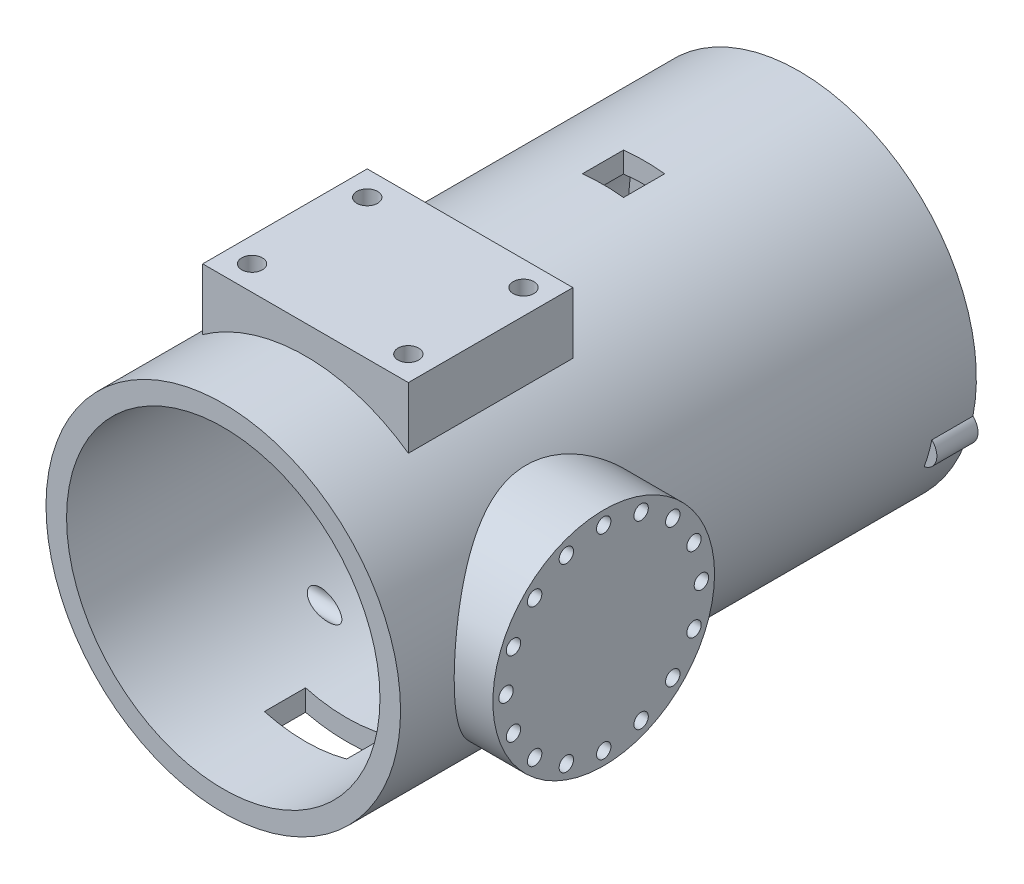
SolidWorks part; units mm, degrees
other "Markup1"
sketch "Sketch14" plane through (-43.1, 43.1, 140) normal (-0.1765, 0.0048, 0.9843) x (0.9842, -0.0149, 0.1765)
other "Markup2"
sketch "Sketch23" plane through (45.1, -43.1, 140) normal (0.9491, -0.0629, 0.3087) x (0.311, 0.031, -0.9499)
ref_plane "Front Plane" through (0, 0, 0) normal (0, 0, 1) x (1, 0, 0)
ref_plane "Top Plane" through (0, 0, 0) normal (0, 1, 0) x (1, 0, 0)
ref_plane "Right Plane" through (0, 0, 0) normal (1, 0, 0) x (0, 0, -1)
sketch "Sketch1" plane through (0, 0, 0) normal (0, 0, 1) x (1, 0, 0)
  circle A1 centre (0, 0) radius 43.1
  dimension "D1" = 86.2
extrude "Main Body" add sketch "Sketch1" along normal blind 140
ref_plane "Plane1" through (0, 43.1, 0) normal (0, 1, 0) x (1, 0, 0)
sketch "Sketch34" [suppressed] plane through (0, 43.1, 0) normal (0, 1, 0) x (1, 0, 0)
  line L6 (-5, -13) -> (5, -13)
  line L8 (-5, -13) -> (-5, -3)
  line L9 (-5, -3) -> (5, -3)
  line L10 (5, -13) -> (5, -3)
  line L11 (-5, -13) -> (5, -3) construction
  line L12 (-5, -3) -> (5, -13) construction
  point P0 (0, -8)
  dimension "D1" = 8
  dimension "D2" = 10
  dimension "D3" = 10
sketch "Sketch6" plane through (0, 43.1, 0) normal (0, 1, 0) x (1, 0, 0)
  line L2 (-5, -47.7) -> (5, -47.7)
  line L3 (-5, -47.7) -> (-5, -37.7)
  line L4 (-5, -37.7) -> (5, -37.7)
  line L5 (5, -47.7) -> (5, -37.7)
  line L6 (-5, -47.7) -> (5, -37.7) construction
  line L7 (-5, -37.7) -> (5, -47.7) construction
  point P2 (0, -42.7)
  dimension "D2" = 10
  dimension "D1" = 42.7
  dimension "D3" = 10
extrude "Cut-Extrude3" cut sketch "Sketch6" against normal through all
ref_plane "Plane2" through (52.5, 0, 0) normal (1, 0, 0) x (0, 0, -1)
sketch "Sketch8" plane through (52.5, 0, 0) normal (1, 0, 0) x (0, 0, -1)
  circle A0 centre (-100, 0) radius 26.95
  dimension "D1" = 53.9
  dimension "D2" = 100
extrude "Boss-Extrude2" add sketch "Sketch8" against normal blind 20
mirror "Mirror1" [suppressed] about plane through (0, 0, 0) normal (1, 0, 0)
ref_plane "Plane3" through (0, 50, 0) normal (0, 1, 0) x (1, 0, 0)
sketch "Sketch33" plane through (0, 50, 0) normal (0, 1, 0) x (1, 0, 0)
  line L1 (-25, -120) -> (25, -120)
  line L2 (-25, -120) -> (-25, -80)
  line L3 (-25, -80) -> (25, -80)
  line L4 (25, -120) -> (25, -80)
  line L5 (-25, -120) -> (25, -80) construction
  line L6 (-25, -80) -> (25, -120) construction
  point P0 (0, -100)
  dimension "D1" = 100
  dimension "D2" = 40
  dimension "D3" = 50
extrude "Boss-Extrude11" add sketch "Sketch33" against normal blind 22
sketch "Sketch35" plane through (0, 50, 0) normal (0, 1, 0) x (1, 0, 0)
  line L0 (-25, -120) -> (-25, -80) construction
  line L1 (25, -120) -> (25, -80) construction
  line L2 (25, -80) -> (-25, -80) construction
  line L3 (-25, -120) -> (25, -120) construction
  circle A0 centre (-19, -86) radius 2.525
  circle A1 centre (19, -86) radius 2.525
  circle A2 centre (-19, -114) radius 2.525
  circle A3 centre (19, -114) radius 2.525
  dimension "D1" = 5.05
  dimension "D2" = 6
  dimension "D3" = 6
  dimension "D4" = 6
  dimension "D5" = 6
extrude "Cut-Extrude14" cut sketch "Sketch35" against normal blind 4
sketch "Sketch5" plane through (0, 0, 140) normal (0, 0, 1) x (1, 0, 0)
  circle A0 centre (0, 0) radius 32
  dimension "D1" = 64
extrude "Hole 1" cut sketch "Sketch5" against normal through all
sketch "Sketch10" plane through (0, 0, 0) normal (0, 1, 0) x (1, 0, 0)
  line L0 (43.1, 0) -> (-43.1, 0) construction
  line L1 (-10, -120) -> (10, -120)
  line L2 (-10, -120) -> (-10, -110)
  line L3 (-10, -110) -> (10, -110)
  line L4 (10, -120) -> (10, -110)
  line L5 (-10, -120) -> (10, -110) construction
  line L6 (-10, -110) -> (10, -120) construction
  point P0 (0, -115)
  point P7 (-10, -115)
  dimension "D1" = 110
  dimension "D2" = 10
  dimension "D3" = 20
extrude "Motor Wire Hole" cut sketch "Sketch10" against normal through all
sketch "Sketch27" plane through (0, 0, 0) normal (1, 0, 0) x (0, 0, -1)
  line L1 (-100, -36.5) -> (-60, -36.5)
  line L2 (-100, -36.5) -> (-100, -27.5)
  line L3 (-100, -27.5) -> (-60, -27.5)
  line L4 (-60, -36.5) -> (-60, -27.5)
  dimension "D1" = 60
  dimension "D2" = 27.5
  dimension "D3" = 40
  dimension "D4" = 9
extrude "Boss-Extrude9" add sketch "Sketch27" along normal blind 33 and the other way blind 33
sketch "Sketch11" plane through (0, 0, 0) normal (1, 0, 0) x (0, 0, -1)
  circle A0 centre (-65, -32) radius 2.25
  circle A1 centre (-95, -32) radius 2.25
  dimension "D3" = 4.5
  dimension "D1" = 65
  dimension "D2" = 32
  dimension "D4" = 30
extrude "Cut-Extrude6" cut sketch "Sketch11" against normal through all both and the other way through all
sketch "Sketch28" plane through (-33, 0, 0) normal (-1, 0, 0) x (0, 0, 1)
  line L0 (62.8927, -28.35) -> (67.1073, -28.35)
  line L1 (67.1073, -28.35) -> (69.2147, -32)
  line L2 (69.2147, -32) -> (67.1073, -35.65)
  line L3 (67.1073, -35.65) -> (62.8927, -35.65)
  line L4 (62.8927, -35.65) -> (60.7853, -32)
  line L6 (60.7853, -32) -> (62.8927, -28.35)
  line L7 (92.8927, -28.35) -> (97.1073, -28.35)
  line L8 (97.1073, -28.35) -> (99.2147, -32)
  line L9 (99.2147, -32) -> (97.1073, -35.65)
  line L10 (97.1073, -35.65) -> (92.8927, -35.65)
  line L11 (92.8927, -35.65) -> (90.7853, -32)
  line L12 (90.7853, -32) -> (92.8927, -28.35)
  circle A0 centre (65, -32) radius 3.65 construction
  circle A1 centre (65, -32) radius 2.25 construction
  circle A2 centre (95, -32) radius 3.65 construction
  circle A3 centre (95, -32) radius 2.25 construction
  dimension "D2" = 7.3
extrude "Cut-Extrude7" cut sketch "Sketch28" against normal blind 3
sketch "Sketch29" plane through (33, 0, 0) normal (1, 0, 0) x (0, 0, -1)
  circle A0 centre (-95, -32) radius 3.6
  circle A1 centre (-65, -32) radius 3.6
  dimension "D1" = 7.2
extrude "Cut-Extrude8" cut sketch "Sketch29" against normal blind 4
sketch "Sketch2" plane through (0, 0, 140) normal (0, 0, 1) x (1, 0, 0)
  circle A0 centre (0, 0) radius 38.1
  dimension "D1" = 76.2
extrude "Cut-Extrude5" cut sketch "Sketch2" against normal blind 135
sketch "Sketch9" plane through (0, 0, 5) normal (0, 0, 1) x (1, 0, 0)
  circle A0 centre (0, 0) radius 38.1
  circle A1 centre (0, 0) radius 36.44
  dimension "D1" = 76.2
  dimension "D2" = 1.66
extrude "Boss-Extrude3" add sketch "Sketch9" along normal blind 10
extrude "Cut-Extrude13" [suppressed] cut sketch "Sketch34" against normal blind 15
sketch "Sketch30" plane through (52.5, 0, 0) normal (1, 0, 0) x (0, 0, -1)
  line L0 (-100, 23.75) -> (-100, 0) construction
  circle A0 centre (-100, 0) radius 23.75 construction
  circle A1 centre (-100, 23.75) radius 1.75
  circle A2 centre (-90.9113, 21.9421) radius 1.75
  circle A3 centre (-83.2062, 16.7938) radius 1.75
  circle A4 centre (-78.0579, 9.0887) radius 1.75
  circle A5 centre (-76.25, 0) radius 1.75
  circle A6 centre (-78.0579, -9.0887) radius 1.75
  circle A7 centre (-83.2062, -16.7938) radius 1.75
  circle A8 centre (-90.9113, -21.9421) radius 1.75
  circle A9 centre (-100, -23.75) radius 1.75
  circle A10 centre (-109.0887, -21.9421) radius 1.75
  circle A11 centre (-116.7938, -16.7938) radius 1.75
  circle A12 centre (-121.9421, -9.0887) radius 1.75
  circle A13 centre (-123.75, 0) radius 1.75
  circle A14 centre (-121.9421, 9.0887) radius 1.75
  circle A15 centre (-116.7938, 16.7938) radius 1.75
  circle A16 centre (-109.0887, 21.9421) radius 1.75
  point P38 (-100, 0)
  dimension "D1" = 47.5
  dimension "D2" = 3.5
  dimension "D3" = 16
extrude "Cut-Extrude9" cut sketch "Sketch30" against normal up to surface (22.7083 mm away) up to face at (38.1, 0, 15)
sketch "Sketch31" plane through (52.5, 0, 0) normal (1, 0, 0) x (0, 0, -1)
  line L0 (0, -43.1) -> (0, 43.1) construction
  line L1 (0, -15) -> (-10, -15)
  line L2 (0, -15) -> (0, -7.5)
  line L3 (0, -7.5) -> (-10, -7.5)
  line L4 (-10, -15) -> (-10, -7.5)
  dimension "D1" = 15
  dimension "D2" = 7.5
  dimension "D3" = 10
extrude "Boss-Extrude10" add sketch "Sketch31" against normal up to body from offset 9 offset against normal yes
sketch "Sketch32" plane through (0, 0, 0) normal (0, 0, -1) x (-1, 0, 0)
  line L0 (-43.5, -11.25) -> (-29.9573, -11.25) construction
  line L1 (-43.5, -15) -> (-43.5, -7.5) construction
  line L3 (-42.4424, -7.5) -> (-43.5, -7.5) construction
  line L5 (-43.5, -15) -> (-43.5, -7.5)
  line L6 (-43.5, -7.5) -> (-42.4424, -7.5)
  circle A0 centre (0, 0) radius 32 construction
  arc A2 (-40.4056, -15) -> (-42.4424, -7.5) centre (0, 0) ccw construction
  arc A3 (-40.4056, -15) -> (-42.2658, -8.4385) centre (-39.6806, -11.25) cw
  arc A4 (-42.2658, -8.4385) -> (-42.4424, -7.5) centre (0, 0) cw
  line M3 (-42.4424, -7.5) -> (-43.5, -7.5)
  line M4 (-43.5, -7.5) -> (-43.5, -15)
  line M5 (-43.5, -15) -> (-40.4056, -15)
extrude "Cut-Extrude10" cut sketch "Sketch32" against normal up to surface (10 mm away) contours M4 M3 | L5 M5 region at (43.0347, -8.5479, 0) region at (42.7123, -14.1508, 0) up to face at (42.5043, -11.2615, 10)
